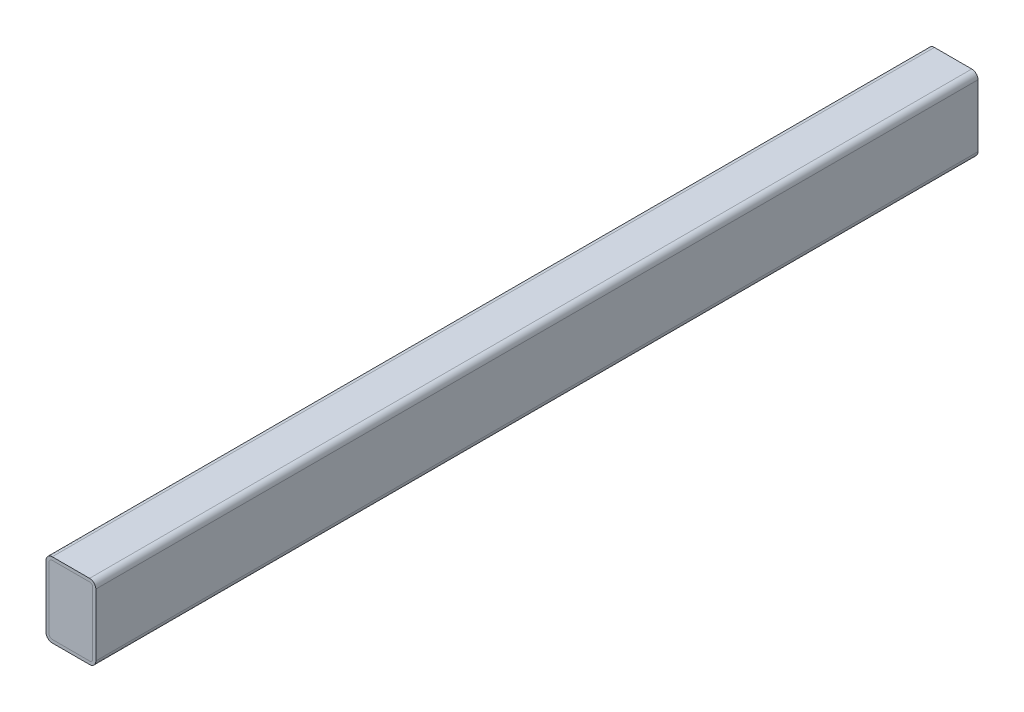
SolidWorks part; units mm, degrees
material "Plain Carbon Steel"
ref_plane "Front Plane" through (0, 0, 0) normal (0, 0, 1) x (1, 0, 0)
ref_plane "Top Plane" through (0, 0, 0) normal (0, 1, 0) x (1, 0, 0)
ref_plane "Right Plane" through (0, 0, 0) normal (1, 0, 0) x (0, 0, -1)
sketch "Sketch13" plane through (0, 0, 0) normal (0, 0, 1) x (1, 0, 0)
  line L4 (19.05, -38.1) -> (-19.05, -38.1)
  line L5 (25.4, 31.75) -> (25.4, -31.75)
  line L6 (-25.4, -31.75) -> (-25.4, 31.75)
  line L7 (-19.05, 38.1) -> (19.05, 38.1)
  line L8 (19.05, -34.925) -> (-19.05, -34.925)
  line L9 (22.225, 31.75) -> (22.225, -31.75)
  line L10 (-19.05, 34.925) -> (19.05, 34.925)
  line L11 (-22.225, -31.75) -> (-22.225, 31.75)
  line L12 (-19.05, 31.75) -> (19.05, -31.75) construction
  line L13 (19.05, 31.75) -> (-19.05, -31.75) construction
  arc A4 (-25.4, -31.75) -> (-19.05, -38.1) centre (-19.05, -31.75) ccw
  arc A5 (19.05, -38.1) -> (25.4, -31.75) centre (19.05, -31.75) ccw
  arc A6 (25.4, 31.75) -> (19.05, 38.1) centre (19.05, 31.75) ccw
  arc A7 (-19.05, 38.1) -> (-25.4, 31.75) centre (-19.05, 31.75) ccw
  arc A8 (-22.225, -31.75) -> (-19.05, -34.925) centre (-19.05, -31.75) ccw
  arc A9 (19.05, -34.925) -> (22.225, -31.75) centre (19.05, -31.75) ccw
  arc A10 (22.225, 31.75) -> (19.05, 34.925) centre (19.05, 31.75) ccw
  arc A11 (-19.05, 34.925) -> (-22.225, 31.75) centre (-19.05, 31.75) ccw
  dimension "D4" = 6.35
  dimension "D2" = 50.8
  dimension "D3" = 76.2
  dimension "D1" = 3.175
extrude "Boss-Extrude2" add sketch "Sketch13" along normal mid plane 899.922 separate body
sketch "Sketch14" plane through (0, 0, 449.961) normal (0, 0, 1) x (1, 0, 0)
  line L0 (-19.05, -34.925) -> (19.05, -34.925) construction
  line L1 (22.225, -31.75) -> (22.225, 31.75) construction
  line L2 (-22.225, 31.75) -> (-22.225, -31.75) construction
  line L3 (19.05, 34.925) -> (-19.05, 34.925) construction
  line L4 (-19.05, -34.925) -> (19.05, -34.925)
  line L5 (22.225, -31.75) -> (22.225, 31.75)
  line L6 (-22.225, 31.75) -> (-22.225, -31.75)
  line L7 (19.05, 34.925) -> (-19.05, 34.925)
  arc A0 (-22.225, -31.75) -> (-19.05, -34.925) centre (-19.05, -31.75) ccw construction
  arc A1 (19.05, -34.925) -> (22.225, -31.75) centre (19.05, -31.75) ccw construction
  arc A2 (22.225, 31.75) -> (19.05, 34.925) centre (19.05, 31.75) ccw construction
  arc A3 (-19.05, 34.925) -> (-22.225, 31.75) centre (-19.05, 31.75) ccw construction
  arc A4 (-22.225, -31.75) -> (-19.05, -34.925) centre (-19.05, -31.75) ccw
  arc A5 (19.05, -34.925) -> (22.225, -31.75) centre (19.05, -31.75) ccw
  arc A6 (22.225, 31.75) -> (19.05, 34.925) centre (19.05, 31.75) ccw
  arc A7 (-19.05, 34.925) -> (-22.225, 31.75) centre (-19.05, 31.75) ccw
extrude "Boss-Extrude3" add sketch "Sketch14" against normal up to surface (899.922 mm away) separate body up to face at (0, 0, -449.961)
equation "\"M5_tap\"=4.2mm       ' Below you can do mesurements as follows: cm, mm, ft, in, m, "
equation "\"M5_clearence\"=5.5mm"
equation "\"M6_tap\"=5mm"
equation "\"M6_clearence\"=6.6mm"
